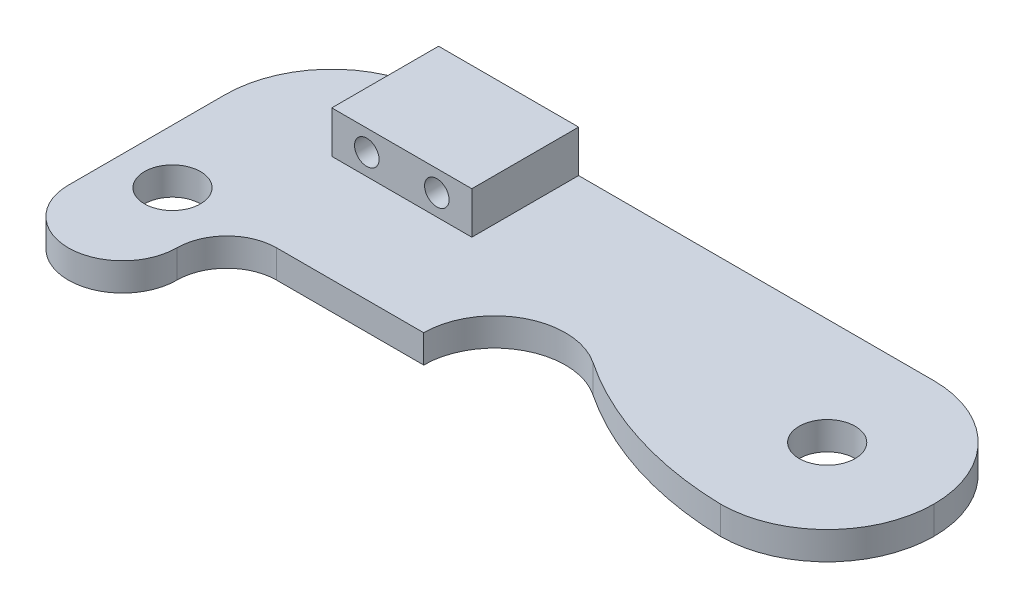
SolidWorks part; units mm, degrees
ref_plane "Front Plane" through (0, 0, 0) normal (0, 0, 1) x (1, 0, 0)
ref_plane "Top Plane" through (0, 0, 0) normal (0, 1, 0) x (1, 0, 0)
ref_plane "Right Plane" through (0, 0, 0) normal (1, 0, 0) x (0, 0, -1)
sketch "Sketch1" plane through (0, 0, 0) normal (0, 1, 0) x (1, 0, 0)
  line L15 (32.8531, -176.6025) -> (73.3531, -176.6025)
  line L17 (41.9031, -188.8025) -> (73.3531, -188.8025)
  line L21 (32.8531, -176.6025) -> (32.8531, -191.6525)
  line L22 (32.8531, -191.6525) -> (39.0531, -191.6525) construction
  line L24 (41.9031, -191.6525) -> (41.9031, -188.8025) construction
  line L28 (73.3531, -176.6025) -> (73.3531, -188.8025)
  arc A14 (41.9031, -188.8025) -> (39.0531, -191.6525) centre (41.9031, -191.6525) ccw
  arc A16 (32.8531, -191.6525) -> (39.0531, -191.6525) centre (35.9531, -191.6525) ccw
  point P8 (73.3531, -182.7025)
  dimension "D1" = 3.1
  dimension "D4" = 2.85
  dimension "D5" = 40.5
  dimension "D6" = 12.2
  dimension "D12" = 90
  dimension "D8" = 6.2
extrude "Boss-Extrude1" add sketch "Sketch1" along normal blind 1.6 contours L21 A16 A14 L17 L15 region at (51.9959, 0, 183.2694)
sketch "Sketch4" plane through (0, 1.6, 0) normal (0, 1, 0) x (1, 0, 0)
  line L0 (32.8531, -176.6025) -> (32.8531, -191.6525) construction
  line L1 (73.3531, -176.6025) -> (73.3531, -188.8025) construction
  line L2 (41.9031, -188.8025) -> (73.3531, -188.8025) construction
  line L3 (73.3531, -176.6025) -> (73.3531, -188.8025) construction
  line L4 (50.3031, -188.8025) -> (58.4031, -188.8025)
  line L6 (32.8531, -176.6025) -> (73.3531, -176.6025) construction
  circle A0 centre (67.2531, -182.7025) radius 1.6
  arc A1 (58.4031, -188.8025) -> (50.3031, -188.8025) centre (54.3531, -188.8025) ccw
  circle A2 centre (35.9531, -188.8025) radius 1.6
  point P17 (35.1673, -176.6025)
  dimension "D1" = 3.2
  dimension "D4" = 8.1
  dimension "D6" = 3.2
  dimension "D2" = 6.1
  dimension "D3" = 6.1
  dimension "D5" = 19
  dimension "D7" = 3.1
  dimension "D8" = 12.2
extrude "Cut-Extrude2" cut sketch "Sketch4" against normal through all
fillet "Fillet2" radius 6.1 3 edges at (73.3531, 0.8, 176.6025) (73.3531, 0.8, 188.8025) (32.8531, 0.8, 176.6025)
sketch "Sketch2" plane through (0, 1.6, 0) normal (0, 1, 0) x (1, 0, 0)
  line L0 (32.8531, -182.7025) -> (32.8531, -191.6525) construction
  line L1 (38.9531, -176.6025) -> (46.9531, -176.6025)
  line L2 (38.9531, -176.6025) -> (38.9531, -182.7025)
  line L3 (38.9531, -182.7025) -> (46.9531, -182.7025)
  line L4 (46.9531, -176.6025) -> (46.9531, -182.7025)
  point P7 (0, 0)
  dimension "D1" = 6.1
  dimension "D2" = 8
  dimension "D3" = 6.1
extrude "Boss-Extrude2" add sketch "Sketch2" along normal blind 2.4
sketch "Sketch3" plane through (0, 0, 176.6025) normal (0, 0, -1) x (-1, 0, 0)
  line L0 (-46.9531, 4) -> (-38.9531, 4) construction
  line L2 (-46.9531, 4) -> (-46.9531, 1.6) construction
  circle A0 centre (-44.9531, 2.8) radius 0.7
  circle A1 centre (-40.9531, 2.8) radius 0.7
  dimension "D5" = 1.4
  dimension "D6" = 1.4
  dimension "D1" = 1.2
  dimension "D2" = 1.2
  dimension "D3" = 4
  dimension "D4" = 2
extrude "Cut-Extrude1" cut sketch "Sketch3" against normal up to next
fillet "Fillet1" radius 20 1 edges at (58.4031, 0.8, 188.8025)
